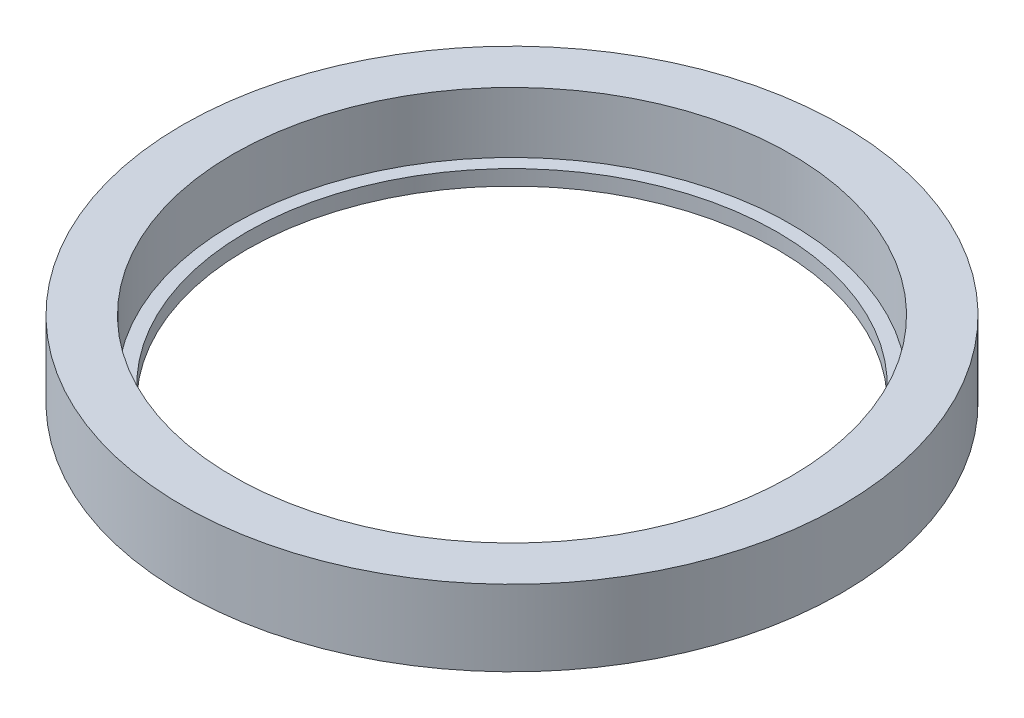
SolidWorks part; units mm, degrees
material "PET"
ref_plane "Front Plane" through (0, 0, 0) normal (0, 0, 1) x (1, 0, 0)
ref_plane "Top Plane" through (0, 0, 0) normal (0, 1, 0) x (1, 0, 0)
ref_plane "Right Plane" through (0, 0, 0) normal (1, 0, 0) x (0, 0, -1)
sketch "Sketch2" plane through (0, 0, 0) normal (0, 0, 1) x (1, 0, 0)
  line L0 (-55.2, -0.2) -> (-52.5, -0.2)
  line L1 (0, 0) -> (-55, 0)
  line L2 (0, 0) -> (0, 8.1)
  line L3 (0, 8.1) -> (-55, 8.1)
  line L4 (-55, 0) -> (-55, 8.1)
  line L5 (-52.5, -0.2) -> (-52.5, -3.2)
  line L6 (-52.5, -3.2) -> (-65.2, -3.2)
  line L7 (-65.2, -3.2) -> (-65.2, 11.8)
  line L12 (-55.2, 11.8) -> (-55.2, -0.2)
  line L13 (-55.2, 11.8) -> (-65.2, 11.8)
  line L14 (0, 0) -> (0, 30.013) construction
sketch "Sketch3" plane through (0, 0, 0) normal (0, 0, 1) x (1, 0, 0)
  line L0 (0, 0) -> (0, 30.013) construction
  line L1 (-55.2, 11.8) -> (-65.2, 11.8) construction
  line L2 (-65.2, -3.2) -> (-65.2, 11.8) construction
  line L3 (-52.5, -3.2) -> (-65.2, -3.2) construction
  line L4 (-52.5, -0.2) -> (-52.5, -3.2) construction
  line L5 (-55.2, -0.2) -> (-52.5, -0.2) construction
  line L6 (-55.2, 11.8) -> (-55.2, -0.2) construction
  line L7 (0, 0) -> (0, 30.013) construction
  line L8 (-55.2, 11.8) -> (-65.2, 11.8)
  line L9 (-65.2, -3.2) -> (-65.2, 11.8)
  line L10 (-52.5, -3.2) -> (-65.2, -3.2)
  line L11 (-52.5, -0.2) -> (-52.5, -3.2)
  line L12 (-55.2, -0.2) -> (-52.5, -0.2)
  line L13 (-55.2, 11.8) -> (-55.2, -0.2)
revolve "Ring" add sketch "Sketch3" angle 360 about L7
